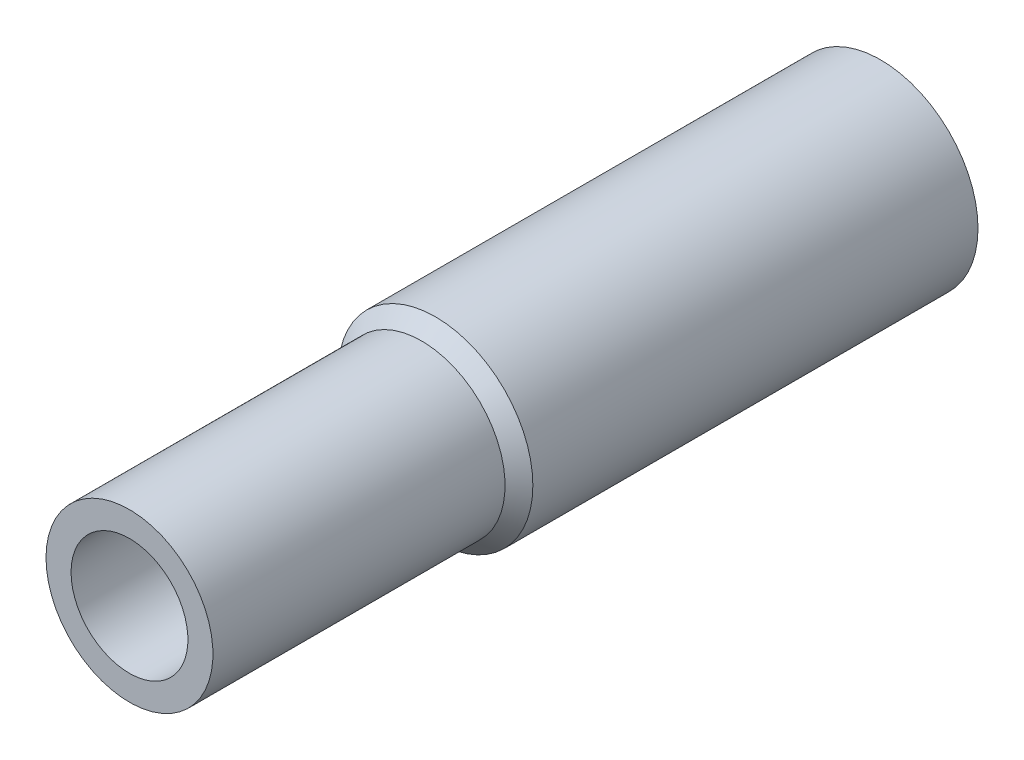
SolidWorks part; units mm, degrees
ref_plane "Płaszczyzna przednia" through (0, 0, 0) normal (0, 0, 1) x (1, 0, 0)
ref_plane "Płaszczyzna górna" through (0, 0, 0) normal (0, 1, 0) x (1, 0, 0)
ref_plane "Płaszczyzna prawa" through (0, 0, 0) normal (1, 0, 0) x (0, 0, -1)
sketch "Sketch1" plane through (0, 0, 0) normal (0, 0, 1) x (1, 0, 0)
  circle A0 centre (0, 0) radius 3.5
  dimension "D1" = 7
extrude "Boss-Extrude1" add sketch "Sketch1" along normal blind 16.5
chamfer "Chamfer1" distance 0.5 1 edges at (3.5, 0, 16.5)
sketch "Sketch2" plane through (0, 0, 16.5) normal (0, 0, 1) x (1, 0, 0)
  circle A0 centre (0, 0) radius 3
  dimension "D1" = 6
extrude "Boss-Extrude2" add sketch "Sketch2" along normal blind 10.5
sketch "Sketch3" plane through (0, 0, 27) normal (0, 0, 1) x (1, 0, 0)
  circle A0 centre (0, 0) radius 2.1
  dimension "D1" = 4.2
hole_wizard "CSK for M4 Flat Head Machine Screw1" positions "Sketch4" profile "Sketch5" countersink size "M4" standard "ANSI Metric" end condition through all
sketch "Sketch4" plane through (0, 0, 0) normal (0, 0, -1) x (-1, 0, 0)
  point P0 (0, 0)
sketch "Sketch5" plane through (0, 0, 0) normal (1, 0, 0) x (0, 1, 0)
  line L0 (0, 0) -> (0, 27)
  line L1 (0, 27) -> (2.1, 27)
  line L2 (2.1, 27) -> (2.1, 0.65)
  line L3 (2.1, 0.65) -> (2.75, 0)
  line L5 (2.75, 0) -> (0, 0)
  line L6 (-2.1, 0.65) -> (-2.75, 0) construction
  line L11 (0, -6.35) -> (0, 107.95) construction
  dimension "Thru Hole Dia." = 4.2
  dimension "Thru Hole Depth" = 27
  dimension "Near C'Sink Dia." = 5.5
  dimension "Near C'Sink Angle" = 90
